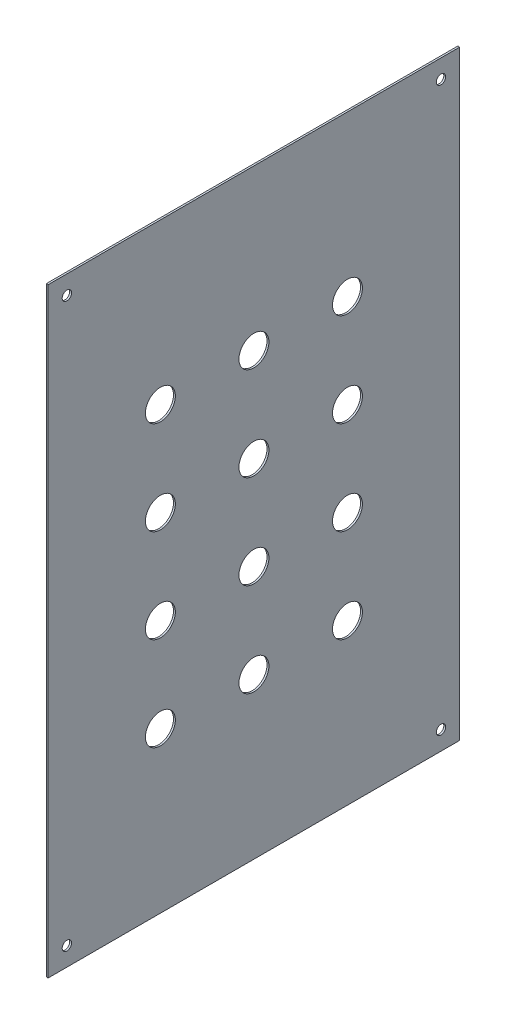
SolidWorks part; units mm, degrees
ref_plane "Front Plane" through (0, 0, 0) normal (1, 0, 0) x (0, 1, 0)
ref_plane "Top Plane" through (0, 0, 0) normal (0, 0, 1) x (0, 1, 0)
ref_plane "Right Plane" through (0, 0, 0) normal (0, 1, 0) x (-1, 0, 0)
sketch "Sketch1" plane through (0, 0, 0) normal (1, 0, 0) x (0, 1, 0)
  line L1 (-160.5, -110) -> (160.5, -110)
  line L2 (-160.5, -110) -> (-160.5, 110)
  line L3 (-160.5, 110) -> (160.5, 110)
  line L4 (160.5, -110) -> (160.5, 110)
  line L5 (-160.5, -110) -> (160.5, 110) construction
  line L6 (-160.5, 110) -> (160.5, -110) construction
  point P0 (0, 0)
  dimension "D1" = 321
  dimension "D2" = 220
extrude "Boss-Extrude1" add sketch "Sketch1" along normal blind 1
sketch "Sketch2" plane through (1, 0, 0) normal (1, 0, 0) x (0, 1, 0)
  line L0 (0, 0) -> (-75, 0) construction
  line L1 (-75, 0) -> (-75, 50) construction
  circle A0 centre (-75, 50) radius 8
  circle A1 centre (-25, 50) radius 8
  circle A2 centre (25, 50) radius 8
  circle A3 centre (75, 50) radius 8
  circle A4 centre (-25, 0) radius 8
  circle A5 centre (25, 0) radius 8
  circle A6 centre (75, 0) radius 8
  circle A7 centre (-25, -50) radius 8
  circle A8 centre (25, -50) radius 8
  circle A9 centre (75, -50) radius 8
  circle A10 centre (-75, 0) radius 8
  circle A11 centre (-75, -50) radius 8
  dimension "D1" = 16
  dimension "D6" = 50
  dimension "D4" = 75
  dimension "D5" = 50
  dimension "D2" = 4
  dimension "D3" = 3
extrude "Cut-Extrude1" cut sketch "Sketch2" against normal through all
sketch "Sketch3" plane through (1, 0, 0) normal (1, 0, 0) x (0, 1, 0)
  line L0 (0, 110) -> (0, -110) construction
  line L1 (160.5, 110) -> (-160.5, 110) construction
  line L2 (-160.5, -110) -> (160.5, -110) construction
  line L4 (-160.5, 110) -> (-160.5, -110) construction
  line L5 (-160.5, 0) -> (160.5, 0) construction
  line L6 (160.5, -110) -> (160.5, 110) construction
  circle A0 centre (-150.5, 100) radius 2.5
  circle A1 centre (150.5, 100) radius 2.5
  circle A2 centre (-150.5, -100) radius 2.5
  circle A3 centre (150.5, -100) radius 2.5
  dimension "D3" = 5
  dimension "D1" = 10
  dimension "D2" = 10
extrude "Cut-Extrude2" cut sketch "Sketch3" against normal through all
